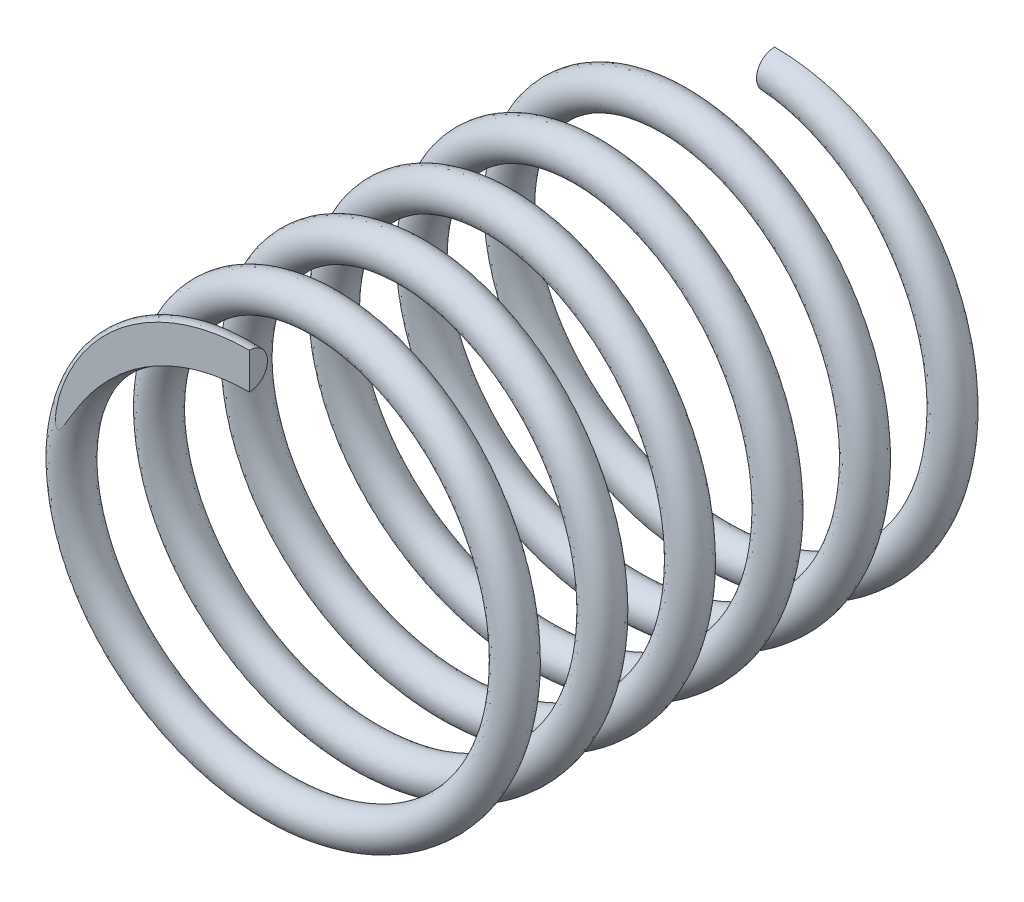
SolidWorks part; units mm, degrees
ref_plane "Plan de face" through (0, 0, 0) normal (0, 0, 1) x (1, 0, 0)
ref_plane "Plan de dessus" through (0, 0, 0) normal (0, 1, 0) x (1, 0, 0)
ref_plane "Plan de droite" through (0, 0, 0) normal (1, 0, 0) x (0, 0, -1)
sketch "Esquisse1" plane through (0, 0, 0) normal (0, 0, 1) x (1, 0, 0)
  circle A0 centre (0, 0) radius 5.5
  dimension "D1" = 11
curve "Hélice/Spirale1" pitch 2.4167 height 14.5 radius 5.5 left hand yes centre (0, 0, 0) axis (0, 0, 1) start towards (0, 1, 0)
sketch "Esquisse3" plane through (0, 0, 0) normal (1, 0, 0) x (0, 0, -1)
  circle A0 centre (0, 5.5) radius 0.5
  spline S0 degree 3 poles (0, 5.5) (-0.05, 5.5) (-0.1512, 5.2136) (-0.302, 3.9903) (-0.4531, 2.1596) (-0.6042, 0) (-0.7552, -2.1596) (-0.9062, -3.9903) (-1.0573, -5.2136) (-1.2083, -5.6432) (-1.3594, -5.2136) (-1.5104, -3.9903) (-1.6615, -2.1596) (-1.8125, 0) (-1.9635, 2.1596) (-2.1146, 3.9903) (-2.2656, 5.2136) (-2.4167, 5.6432) (-2.5677, 5.2136) (-2.7187, 3.9903) (-2.8698, 2.1596) (-3.0208, 0) (-3.1719, -2.1596) (-3.3229, -3.9903) (-3.474, -5.2136) (-3.625, -5.6432) (-3.776, -5.2136) (-3.9271, -3.9903) (-4.0781, -2.1596) (-4.2292, 0) (-4.3802, 2.1596) (-4.5312, 3.9903) (-4.6823, 5.2136) (-4.8333, 5.6432) (-4.9844, 5.2136) (-5.1354, 3.9903) (-5.2865, 2.1596) (-5.4375, 0) (-5.5885, -2.1596) (-5.7396, -3.9903) (-5.8906, -5.2136) (-6.0417, -5.6432) (-6.1927, -5.2136) (-6.3437, -3.9903) (-6.4948, -2.1596) (-6.6458, 0) (-6.7969, 2.1596) (-6.9479, 3.9903) (-7.099, 5.2136) (-7.25, 5.6432) (-7.401, 5.2136) (-7.5521, 3.9903) (-7.7031, 2.1596) (-7.8542, 0) (-8.0052, -2.1596) (-8.1562, -3.9903) (-8.3073, -5.2136) (-8.4583, -5.6432) (-8.6094, -5.2136) (-8.7604, -3.9903) (-8.9115, -2.1596) (-9.0625, 0) (-9.2135, 2.1596) (-9.3646, 3.9903) (-9.5156, 5.2136) (-9.6667, 5.6432) (-9.8177, 5.2136) (-9.9688, 3.9903) (-10.1198, 2.1596) (-10.2708, 0) (-10.4219, -2.1596) (-10.5729, -3.9903) (-10.724, -5.2136) (-10.875, -5.6432) (-11.026, -5.2136) (-11.1771, -3.9903) (-11.3281, -2.1596) (-11.4792, 0) (-11.6302, 2.1596) (-11.7813, 3.9903) (-11.9323, 5.2136) (-12.0833, 5.6432) (-12.2344, 5.2136) (-12.3854, 3.9903) (-12.5365, 2.1596) (-12.6875, 0) (-12.8385, -2.1596) (-12.9896, -3.9903) (-13.1406, -5.2136) (-13.2917, -5.6432) (-13.4427, -5.2136) (-13.5938, -3.9903) (-13.7448, -2.1596) (-13.8958, 0) (-14.0469, 2.1596) (-14.198, 3.9903) (-14.3488, 5.2136) (-14.45, 5.5) (-14.5, 5.5) knots 0 0 0 0 0.010417 0.020833 0.03125 0.041667 0.052083 0.0625 0.072917 0.083333 0.09375 0.104167 0.114583 0.125 0.135417 0.145833 0.15625 0.166667 0.177083 0.1875 0.197917 0.208333 0.21875 0.229167 0.239583 0.25 0.260417 0.270833 0.28125 0.291667 0.302083 0.3125 0.322917 0.333333 0.34375 0.354167 0.364583 0.375 0.385417 0.395833 0.40625 0.416667 0.427083 0.4375 0.447917 0.458333 0.46875 0.479167 0.489583 0.5 0.510417 0.520833 0.53125 0.541667 0.552083 0.5625 0.572917 0.583333 0.59375 0.604167 0.614583 0.625 0.635417 0.645833 0.65625 0.666667 0.677083 0.6875 0.697917 0.708333 0.71875 0.729167 0.739583 0.75 0.760417 0.770833 0.78125 0.791667 0.802083 0.8125 0.822917 0.833333 0.84375 0.854167 0.864583 0.875 0.885417 0.895833 0.90625 0.916667 0.927083 0.9375 0.947917 0.958333 0.96875 0.979167 0.989583 1 1 1 1 construction
  dimension "D1" = 1
sweep "Balayage1" add profiles "Esquisse3" path "Hélice/Spirale1"
sketch "Esquisse4" plane through (0, 0, 0) normal (1, 0, 0) x (0, 0, -1)
  line L1 (-14.5, 10.0235) -> (-16.8791, 10.0235)
  line L2 (-14.5, 10.0235) -> (-14.5, -9.4899)
  line L3 (-14.5, -9.4899) -> (-16.8791, -9.4899)
  line L4 (-16.8791, 10.0235) -> (-16.8791, -9.4899)
  dimension "D1" = 14.5
extrude "Enlèv. mat.-Extru.1" cut sketch "Esquisse4" against normal through all
sketch "Esquisse5" plane through (0, 0, 0) normal (-1, 0, 0) x (0, 0, 1)
  line L1 (0, 10.0616) -> (-2.1466, 10.0616)
  line L2 (0, 10.0616) -> (0, -8.6781)
  line L3 (0, -8.6781) -> (-2.1466, -8.6781)
  line L4 (-2.1466, 10.0616) -> (-2.1466, -8.6781)
extrude "Enlèv. mat.-Extru.2" cut sketch "Esquisse5" against normal through all
ref_axis "Axis1" through (0, 0, -1.275) along (0, 0, 1)
